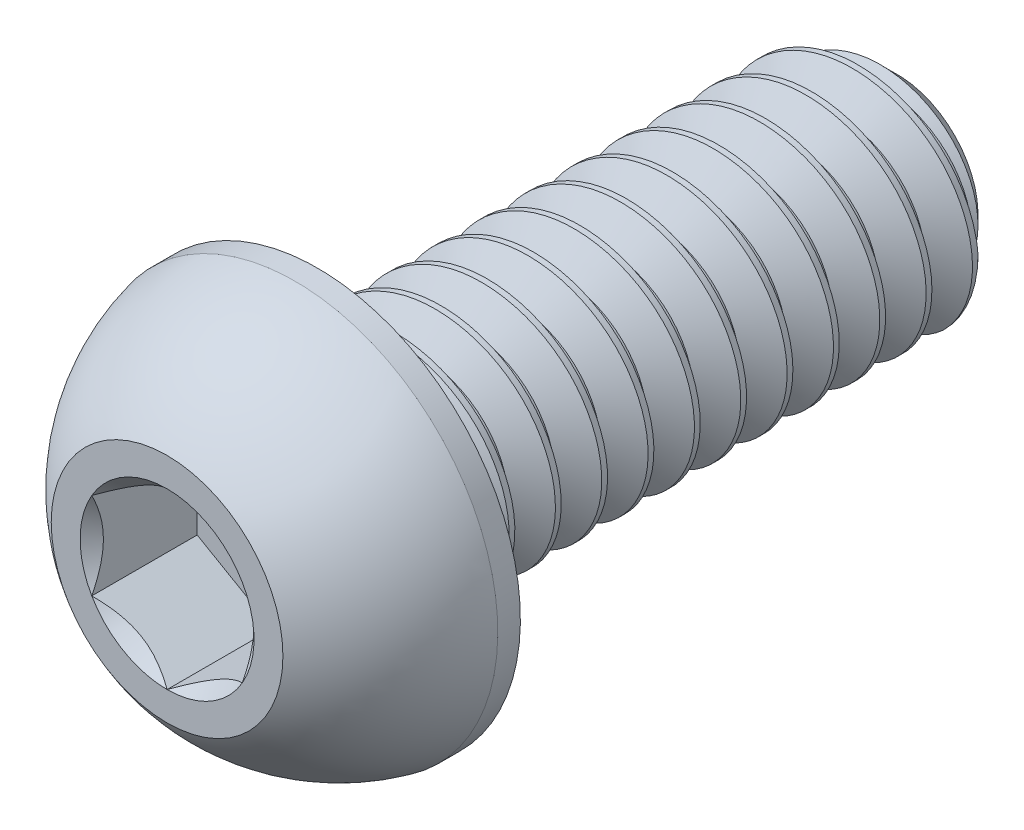
SolidWorks part; units mm, degrees
ref_plane "Front" through (0, 0, 0) normal (0, 0, 1) x (1, 0, 0)
ref_plane "Top" through (0, 0, 0) normal (0, 1, 0) x (1, 0, 0)
ref_plane "Right" through (0, 0, 0) normal (1, 0, 0) x (0, 0, -1)
sketch "Sketch1" plane through (0, 0, 0) normal (1, 0, 0) x (0, 0, -1)
  line L2 (-2.5, 1) -> (2.5, 1)
  line L3 (2.5, 1) -> (2.5, 0)
  line L4 (2.5, 0) -> (-2.5, 0)
  line L6 (-2.695, 1.75) -> (-2.5, 1.75) construction
  line L7 (2.5, 1) -> (2.5, -1) construction
  line L8 (-3.8, 0) -> (-2.5, 0) construction
  line L9 (-2.5, 1.75) -> (-2.5, -1.75) construction
  line L11 (-2.5, 1) -> (-2.5, 0)
  line L13 (-3.8, 0.65) -> (-3.8, -0.65) construction
  line L14 (-3.8, 0.65) -> (-3.8, 1) construction
  line L15 (2.475, 1.0433) -> (2.675, 0.6969) construction
  line L16 (2.675, 0.6969) -> (2.875, 1.0433) construction
  line L17 (2.875, 1.0433) -> (2.475, 1.0433) construction
  line L18 (2.5, 1) -> (2.85, 1) construction
  line L19 (2.675, 1.0433) -> (2.675, 1) construction
  line L20 (2.675, 1) -> (2.675, 0.7402) construction
  line L21 (2.675, 0.7402) -> (2.675, 0.6969) construction
  line L22 (2.65, 0.7402) -> (2.7, 0.7402)
  line L23 (2.4875, 1.0217) -> (2.8625, 1.0217)
  line L24 (2.7, 0.7402) -> (2.8625, 1.0217)
  line L25 (2.65, 0.7402) -> (2.4875, 1.0217)
  line L26 (2.2, 1) -> (2.5, 0.7)
  arc A3 (-3.8, 1) -> (-2.695, 1.75) centre (-2.3142, 0) cw construction
  point P29 (2.675, 1.0217)
  point P30 (1.5, -1)
  point P33 (0, 0)
  dimension "Thread Size" = 2
  dimension "D1" = 0.195
  dimension "Head Height" = 1.3
  dimension "Head Diameter" = 3.5
  dimension "Length" = 5
  dimension "Drive Size" = 1.3
  dimension "Thread Pitch" = 0.4
  dimension "D3" = 0.05
  dimension "D2" = 0.3
  dimension "D4" = 45
  dimension "D5" = 1
sketch "Sketch10" plane through (0, 0, 0) normal (1, 0, 0) x (0, 0, -1)
  line L0 (2.2, 1) -> (2.5, 0.7) construction
  line L1 (2.2, 1) -> (2.5, 0.7)
  line L4 (2.5, 1) -> (-2.5, 1)
  line L5 (2.5, 0) -> (2.5, 1)
  line L6 (-2.5, 0) -> (2.5, 0)
  line L7 (-2.5, 1) -> (-2.5, 0)
  line L8 (2.2, 1) -> (-2.5, 1)
  line L9 (2.5, 0) -> (2.5, 0.7)
  line L10 (-2.5, 0) -> (2.5, 0)
  line L11 (-2.5, 1) -> (-2.5, 0)
  dimension "D1" = 0
revolve "Revolve3" add sketch "Sketch10" angle 360 about L8
sketch "Sketch7" plane through (0, 0, 0) normal (1, 0, 0) x (0, 0, -1)
  line L6 (-2.695, 1.75) -> (-2.5, 1.75) construction
  line L8 (-3.8, 0) -> (-2.5, 0) construction
  line L11 (-2.5, 1.75) -> (-2.5, -1.75) construction
  line L12 (-2.695, 1.75) -> (-2.5, 1.75)
  line L13 (-3.8, 0) -> (-2.5, 0)
  line L14 (-3.8, 0.65) -> (-3.8, -0.65) construction
  line L15 (-2.5, 1.75) -> (-2.5, 0)
  line L16 (-3.8, 1) -> (-3.8, 0)
  arc A2 (-2.695, 1.75) -> (-3.8, 1) centre (-2.3142, 0) ccw construction
  arc A3 (-2.695, 1.75) -> (-3.8, 1) centre (-2.3142, 0) ccw
revolve "Revolve2" add sketch "Sketch7" angle 360 mid plane about L13
sketch "Sketch5" plane through (0, 0, 3.8) normal (0, 0, 1) x (1, 0, 0)
  line L1 (0.65, -0.3753) -> (0.65, 0.3753)
  line L2 (0.65, 0.3753) -> (0, 0.7506)
  line L3 (0, 0.7506) -> (-0.65, 0.3753)
  line L4 (-0.65, 0.3753) -> (-0.65, -0.3753)
  line L5 (-0.65, -0.3753) -> (0, -0.7506)
  line L6 (0, -0.7506) -> (0.65, -0.3753)
  circle A0 centre (0, 0) radius 0.65 construction
extrude "Cut-Extrude2" cut sketch "Sketch5" against normal blind 0.91
sketch "Sketch6" plane through (0, 0, 3.8) normal (0, 0, 1) x (1, 0, 0)
  circle A0 centre (0, 0) radius 0.7506
extrude "Cut-Extrude3" cut sketch "Sketch6" against normal blind 0.91 draft 45
sketch "Sketch9" plane through (0, 0, 2.5) normal (0, 0, -1) x (-1, 0, 0)
  circle A0 centre (0, 0) radius 1 construction
  circle A4 centre (0, 0) radius 1
split "Split1" bodies to split 113 resulting bodies 123 124 split by face at (0, -1.75, 2.5)
sketch "Sketch11" plane through (0, 0, -2.5) normal (0, 0, -1) x (-1, 0, 0)
  circle A0 centre (0, 0) radius 1 construction
  circle A1 centre (0, 0) radius 1
curve "Helix/Spiral1" pitch 0.4 height 6.3 radius 1 centre (0, 0, -2.5) axis (0, 0, 1) start towards (0, 1, 0)
sketch "Sketch12" plane through (0, 0, 0) normal (1, 0, 0) x (0, 0, -1)
  line L0 (2.65, 0.7402) -> (2.7, 0.7402) construction
  line L1 (2.7, 0.7402) -> (2.8625, 1.0217) construction
  line L2 (2.4875, 1.0217) -> (2.8625, 1.0217) construction
  line L3 (2.65, 0.7402) -> (2.4875, 1.0217) construction
  line L4 (2.65, 0.7402) -> (2.7, 0.7402)
  line L5 (2.7, 0.7402) -> (2.8625, 1.0217)
  line L6 (2.4875, 1.0217) -> (2.8625, 1.0217)
  line L7 (2.65, 0.7402) -> (2.4875, 1.0217)
sweep "Cut-Sweep2" cut profiles "Sketch12" path "Helix/Spiral1" align with end faces yes
extrude "Boss-Extrude1" add sketch "Sketch9" along normal blind 10 draft 45
equation "\"D1@Cut-Extrude2\" = \"Head Height@Sketch1\" * .7"
equation "\"D1@Sketch1\" = \"Head Height@Sketch1\" * .15"
equation "\"D1@Cut-Extrude3\" = \"D1@Cut-Extrude2\""
equation "\"D3@Sketch1\" = \"Thread Pitch@Sketch1\" / 8"
equation "\"D2@Sketch1\" = \"Thread Pitch@Sketch1\" * 0.75"
equation "\"D3@Helix/Spiral1\" = \"Length@Sketch1\" + \"Head Height@Sketch1\""
equation "\"D4@Helix/Spiral1\" = \"Thread Pitch@Sketch1\""
equation "\"D5@Sketch1\" = \"Thread Pitch@Sketch1\" * 2.5"
